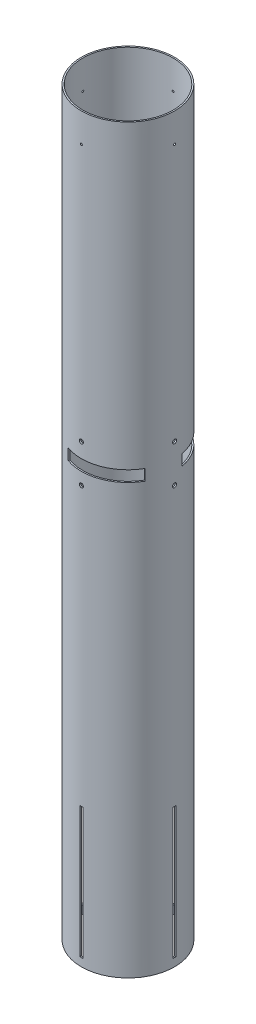
SolidWorks part; units mm, degrees
material "A-Glass Fiber"
ref_plane "Front Plane" through (0, 0, 0) normal (0, 0, 1) x (1, 0, 0)
ref_plane "Top Plane" through (0, 0, 0) normal (0, 1, 0) x (1, 0, 0)
ref_plane "Right Plane" through (0, 0, 0) normal (1, 0, 0) x (0, 0, -1)
sketch "Sketch1" plane through (0, 0, 0) normal (0, 1, 0) x (1, 0, 0)
  circle A0 centre (0, 0) radius 49.53
  circle A1 centre (0, 0) radius 51.1048
  dimension "D1" = 99.06
  dimension "D2" = 102.2096
extrude "Boss-Extrude1" add sketch "Sketch1" along normal blind 812.8
ref_plane "Plane1" through (0, 0, 0) normal (0.7071, 0, 0.7071) x (0.7071, 0, -0.7071)
ref_axis "Axis1" through (0, 812.8, 0) along (0, -1, 0)
sketch "Sketch2" plane through (0, 0, 0) normal (1, 0, 0) x (0, 0, -1)
  line L0 (0, 0) -> (0, 8.89)
  line L1 (1.5875, 8.89) -> (-1.5875, 8.89)
  line L2 (1.5875, 8.89) -> (1.5875, 152.4)
  line L3 (1.5875, 152.4) -> (-1.5875, 152.4)
  line L4 (-1.5875, 8.89) -> (-1.5875, 152.4)
  line L5 (1.5875, 8.89) -> (-1.5875, 152.4) construction
  line L6 (1.5875, 152.4) -> (-1.5875, 8.89) construction
  line L7 (51.1048, 812.8) -> (-51.1048, 812.8) construction
  line L8 (51.1048, 812.8) -> (-51.1048, 812.8)
  line L9 (0, 812.8) -> (0, 498.95)
  line L10 (-51.1048, 0) -> (51.1048, 0) construction
  circle A0 centre (0, 498.95) radius 2.25
  point P0 (0, 80.645)
  dimension "D4" = 4.5
  dimension "D1" = 3.175
  dimension "D5" = 498.95
  dimension "D3" = 152.4
  dimension "D2" = 8.89
extrude "Cut-Extrude1" cut sketch "Sketch2" against normal through all contours L4 L1 L2 L3 region at (0, 80.645, 0)
pattern_circular "CirPattern1" count 4 over 360 about axis through (0, 0, 0) along (0, 1, 0) of "Cut-Extrude1" reverse direction yes
extrude "Cut-Extrude2" cut sketch "Sketch2<3>" against normal through all contours A0 region at (0, 497.404, 1.546)
sketch "Sketch2<3>" plane through (0, 0, 0) normal (1, 0, 0) x (0, 0, -1) same geometry as "Sketch2"
pattern_circular "CirPattern2" count 4 over 360 about axis through (0, 812.8, 0) along (0, -1, 0) of "Cut-Extrude2"
sketch "Sketch3" plane through (0, 0, 0) normal (0.7071, 0, 0.7071) x (0.7071, 0, -0.7071)
  line L0 (0, 0) -> (0, 127) construction
  circle A0 centre (0, 127) radius 3.175
  dimension "D1" = 6.35
  dimension "D2" = 127
extrude "Cut-Extrude3" cut sketch "Sketch3" against normal through all
sketch "Sketch7" plane through (0, 0, 0) normal (0, 1, 0) x (1, 0, 0)
  line L0 (0, 0) -> (-44.2581, -25.5524)
  line L1 (0, 0) -> (0, 93.232) construction
  line L2 (0, 0) -> (-32.8495, 39.1485)
  line L3 (-51.1048, 0) -> (0, 0) construction
  arc A0 (-51.0552, 2.25) -> (-51.0552, -2.25) centre (0, 0) ccw construction
  circle A1 centre (0, 0) radius 49.53 construction
  circle A2 centre (0, 0) radius 51.1048
  circle A3 centre (0, 0) radius 51.1048
  circle A4 centre (0, 0) radius 49.53
  circle A5 centre (0, 0) radius 51.1048 construction
  arc A6 (2.25, 51.0552) -> (-2.25, 51.0552) centre (0, 0) ccw construction
  arc A7 (-51.0552, 2.25) -> (-51.0552, -2.25) centre (0, 0) ccw
  arc A8 (2.25, 51.0552) -> (-2.25, 51.0552) centre (0, 0) ccw
  dimension "D1" = 80
  dimension "D3" = 30
  dimension "D2" = 0
extrude "Cut-Extrude4" cut sketch "Sketch7" against normal blind 12.065 from offset 482.6 contours A4 A3 L0 region at (-43.9137, 0, 24.5741)
pattern_circular "CirPattern3" count 3 over 360 about axis through (0, 812.8, 0) along (0, -1, 0) of "Cut-Extrude4"
pattern_linear "LPattern1" count 2 spacing 41.6916 along (0, -1, 0) of "CirPattern2"
sketch "Sketch8" plane through (0, 0, 0) normal (0, 0, 1) x (1, 0, 0)
  line L0 (49.53, 812.8) -> (-49.53, 812.8) construction
  circle A0 centre (0, 781.05) radius 1.0922
  dimension "D1" = 2.1844
  dimension "D2" = 31.75
extrude "Cut-Extrude5" cut sketch "Sketch8" against normal through all
pattern_circular "CirPattern4" count 4 over 360 about axis through (0, 812.8, 0) along (0, -1, 0) of "Cut-Extrude5"
sketch "Sketch9" plane through (0, 0, 0) normal (0, 0, 1) x (1, 0, 0)
  line L0 (51.1048, 812.8) -> (-51.1048, 812.8) construction
  point P0 (0, 752.856)
  dimension "D1" = 59.944
hole_wizard "1/2 Clearance Hole4" positions "Sketch17" profile "Sketch18" hole size "1/2" standard "ANSI Inch" end condition through all
sketch "Sketch17" plane through (0, 0, 0) normal (0, 0, 1) x (1, 0, 0)
  line L0 (51.1048, 812.8) -> (-51.1048, 812.8) construction
  point P0 (0, 752.856)
  dimension "D1" = 752.856
  dimension "D2" = 59.944
sketch "Sketch18" plane through (0, 752.856, 0) normal (1, 0, 0) x (0, -1, 0)
  line L0 (0, 0) -> (0, 51.1048)
  line L1 (0, 51.1048) -> (6.5481, 51.1048)
  line L2 (6.5481, 51.1048) -> (6.5481, 0)
  line L5 (6.5481, 0) -> (0, 0)
  line L11 (0, -6.35) -> (0, 107.95) construction
  dimension "Thru Hole Dia." = 13.0962
  dimension "Thru Hole Depth" = 51.1048
ref_plane "Plane3" through (24.3888, 0, -29.0654) normal (0.6428, 0, -0.766) x (-0.766, 0, -0.6428)
equation "\"D1@Boss-Extrude1\" = \"Aft_Section_Length\""
equation "\"AB_Coupler_OD_Length\"= 1in"
equation "\"AB_Coupling_Section_Length\"= 0.375in"
equation "\"AB_Coupler_Length\"= \"AB_Coupler_OD_Length\" + \"AB_Coupling_Section_Length\" * 2"
equation "\"AB_Coupler_Num_Screws\"= 4"
equation "\"AB_Coupling_Screw_Diameter\"= 4.5mm"
equation "\"Aft_Section_Length\" = 32in"
equation "\"D4@Sketch2\"=\"AB_Coupling_Screw_Diameter\""
equation "\"D1@CirPattern2\"=\"AB_Coupler_Num_Screws\""
equation "\"Rail_Nut_From_Bottom\"= 5in"
equation "\"Rail_Nut_Diam\"= 0.25in"
equation "\"D1@Sketch3\"=\"Rail_Nut_Diam\""
equation "\"D2@Sketch3\"=\"Rail_Nut_From_Bottom\""
equation "\"AB_BKHD_Thickness\"= 0.375in"
equation "\"AB_Mount_From_Bottom\"= 19.25in"
equation "\"Cutout_Angle\" = 60"
equation "\"Motor_OD\" = 54.4mm"
equation "\"Motor_Length\" = 401mm"
equation "\"Mid_Coupler_Length\" = 12in"
equation "\"AB_Paddle_Height\" = 0.375in"
equation "\"Num_Cutouts\" = 4"
equation "\"AB_Coupler_OD\"= 4.024in"
equation "\"AB_Coupler_ID\"= 3.7in"
equation "\"AB_Coupler_Surface_Diameter\"= 3.899in"
equation "\"AB_Central_Bushing_Length\" = 0.75in"
equation "\"Lead_Screw_Dist\" = 2in"
equation "\"Lead_Screw_Diam\" = 0.375in"
equation "\"Lead_Screw_Length\" = \"Mid_Coupler_Length\" + 2*0.375in + 2*0.5in"
equation "\"Paddle_Pin_Offset\" = 0.25in"
equation "\"Paddle_Pin_Radius\" = 2.25*2/3in"
equation "\"Paddle_Gear_OD\" = 3.2in"
equation "\"Fwd_BKHD_From_Top\" = 18in"
equation "\"Body_Tube_OD\"= 4.024in"
equation "\"Body_Tube_ID\"= 3.90in"
equation "\"Coupler_OD\" = 3.899in"
equation "\"Coupler_ID\" = 3.755in"
equation "\"Fwd_Section_Length\" = 20in"
equation "\"Mid_Section_Length\" = 4in"
equation "\"Aft_Upper_Tube_Length\" = 10in"
equation "\"Aft_Lower_Tube_Length\" = 18in"
equation "\"Nosecone_Coupler_Length\" = 5in"
equation "\"Avionics_Bulkhead_Thickness\" = 0.25in"
equation "\"Avionics_Bulkhead_Lip\" = 0.125in"
equation "\"Avionics_Board_Length\" = \"Mid_Coupler_Length\" - 2*\"Avionics_Bulkhead_Lip\""
equation "\"Lead_Screw_Hole_Diam\" = 0.386in"
equation "\"Centering_Ring_Cutout_Dia\"= 1in"
equation "\"D2@Sketch1\"=\"Body_Tube_OD\""
equation "\"D1@Sketch1\"=\"Body_Tube_ID\""
equation "\"D5@Sketch2\"=\"AB_Mount_From_Bottom\"+0.393701"
equation "\"D19@Cut-Extrude4\"=\"AB_Mount_From_Bottom\"-0.25"
